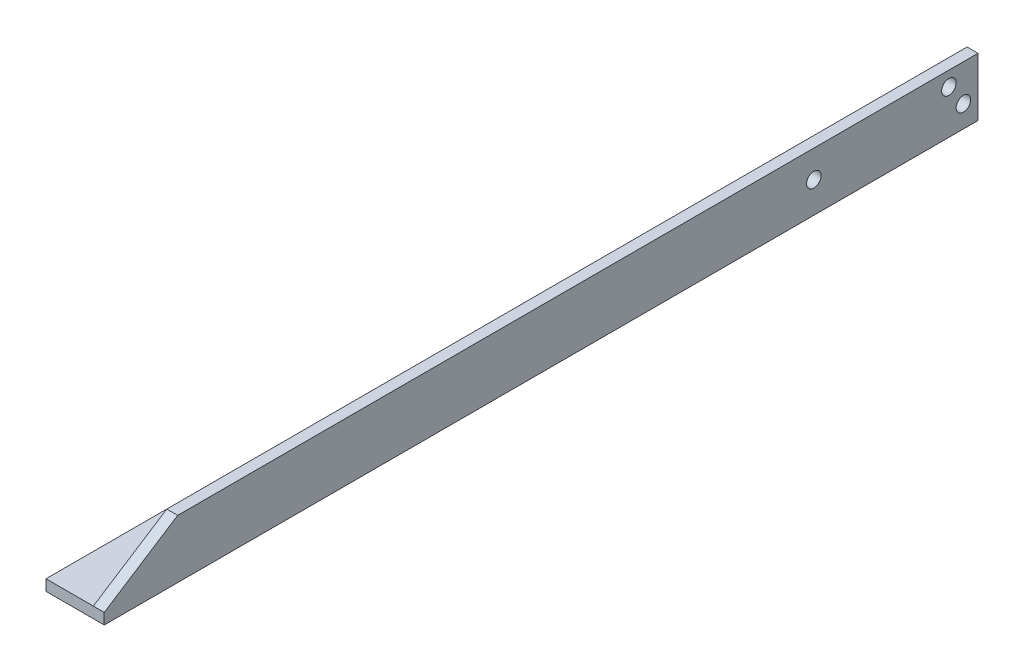
SolidWorks part; units mm, degrees
material "6061 Alloy"
ref_plane "Front Plane" through (0, 0, 0) normal (0, 0, 1) x (1, 0, 0)
ref_plane "Top Plane" through (0, 0, 0) normal (0, 1, 0) x (1, 0, 0)
ref_plane "Right Plane" through (0, 0, 0) normal (1, 0, 0) x (0, 0, -1)
sketch "Sketch1" plane through (0, 0, 0) normal (0, 0, 1) x (1, 0, 0)
  line L0 (0, 0) -> (0, -25.4)
  line L1 (0, -25.4) -> (-25.4, -25.4)
  line L2 (-4.7625, 0) -> (-4.7625, -20.6375)
  line L3 (-4.7625, -20.6375) -> (-25.4, -20.6375)
  line L4 (-4.7625, 0) -> (0, 0)
  line L5 (-25.4, -25.4) -> (-25.4, -20.6375)
  dimension "D1" = 25.4
  dimension "D2" = 25.4
  dimension "D3" = 4.7625
extrude "Boss-Extrude1" add sketch "Sketch1" along normal blind 381
sketch "Sketch4" plane through (-4.7625, 0, 0) normal (-1, 0, 0) x (0, 0, 1)
  line L0 (381, -20.6375) -> (348.9734, 0)
  line L1 (381, 0) -> (0, 0) construction
  dimension "D1" = 38.1
extrude "Cut-Extrude3" cut sketch "Sketch4" against normal through all and the other way through all flip side to cut
sketch "Sketch6" plane through (-4.7625, 0, 0) normal (-1, 0, 0) x (0, 0, 1)
  line L0 (348.9734, 0) -> (0, 0) construction
  line L1 (0, 0) -> (0, -20.6375) construction
  circle A0 centre (6.35, -15.875) radius 3.175
  circle A1 centre (12.7, -6.35) radius 3.175
  dimension "D1" = 6.35
  dimension "D2" = 6.35
  dimension "D3" = 6.35
  dimension "D4" = 6.35
  dimension "D5" = 12.7
  dimension "D6" = 15.875
extrude "Cut-Extrude4" cut sketch "Sketch6" against normal up to next
sketch "Sketch7" plane through (0, 0, 0) normal (1, 0, 0) x (0, 0, -1)
  circle A0 centre (-71.5697, -11.9296) radius 3.175 construction
  circle A1 centre (-71.5697, -11.9296) radius 3.175
extrude "Cut-Extrude5" cut sketch "Sketch7" against normal up to next
sketch "Sketch8" plane through (0, -20.6375, 0) normal (0, 1, 0) x (1, 0, 0)
  line L0 (-25.4, -381) -> (-25.4, 0) construction
  line L1 (-4.7625, 0) -> (-25.4, 0) construction
  circle A0 centre (-15.0812, -12.7) radius 3.175
  dimension "D1" = 6.35
  dimension "D2" = 10.3187
  dimension "D3" = 12.7
extrude "Cut-Extrude6" cut sketch "Sketch8" against normal up to next
equation "\"1..500in\"=1"
